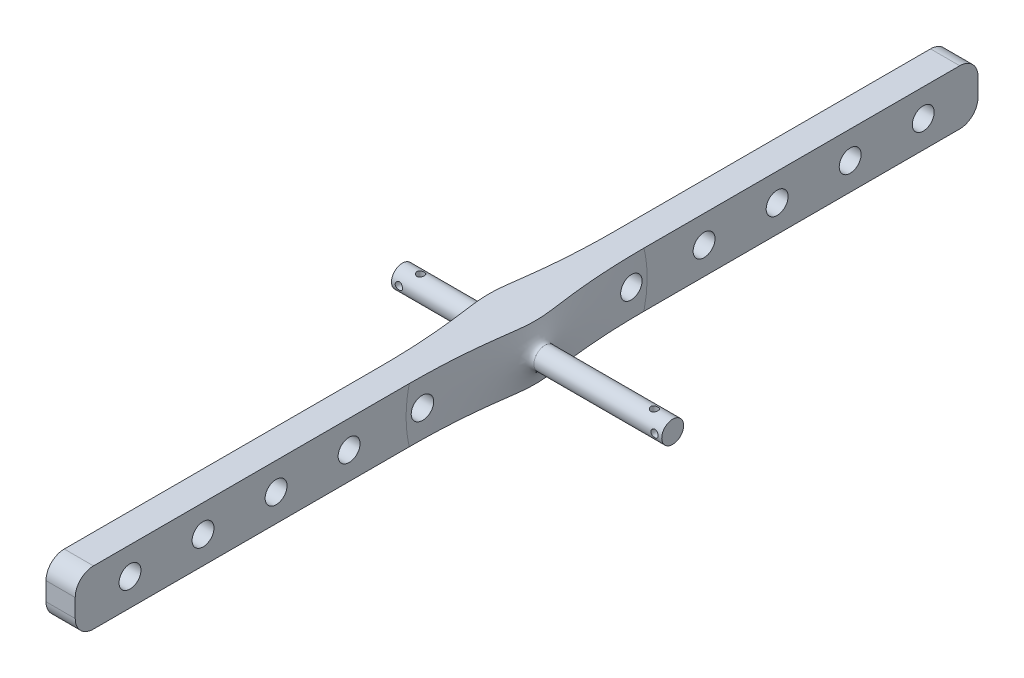
SolidWorks part; units mm, degrees
ref_plane "前视基准面" through (0, 0, 0) normal (0, 0, 1) x (1, 0, 0)
ref_plane "上视基准面" through (0, 0, 0) normal (0, 1, 0) x (1, 0, 0)
ref_plane "右视基准面" through (0, 0, 0) normal (1, 0, 0) x (0, 0, -1)
other "Configuration Table"
sketch "草图1" plane through (0, 0, 0) normal (1, 0, 0) x (0, 0, -1)
  line L1 (0, 0) -> (130, 0)
  line L2 (0, 0) -> (0, 15)
  line L3 (0, 15) -> (130, 15)
  line L4 (130, 0) -> (130, 15)
  dimension "D1" = 15
  dimension "D2" = 130
extrude "凸台-拉伸1" add sketch "草图1" along normal blind 8
sketch "草图15" plane through (0, 0, 0) normal (-1, 0, 0) x (0, 0, 1)
  line L0 (0, 15) -> (0, 0) construction
  circle A2 centre (-6.4, 7.5) radius 3
  dimension "D1" = 6
  dimension "D2" = 6.4
extrude "凸台-拉伸5" add sketch "草图15" along normal blind 26 and the other way blind 48
sketch "草图16" plane through (0, 0, 0) normal (0, 0, 1) x (1, 0, 0)
  line L0 (-26, 7.5) -> (-24.7951, 7.5) construction
  line L1 (-26, 10.5) -> (-26, 4.5) construction
  line L2 (48, 7.5) -> (28.4852, 7.5) construction
  line L3 (48, 4.5) -> (48, 10.5) construction
  circle A0 centre (-24, 7.5) radius 1
  circle A1 centre (46, 7.5) radius 1
  dimension "D2" = 2
  dimension "D3" = 2
  dimension "D1" = 2
  dimension "D4" = 2
extrude "切除-拉伸9" cut sketch "草图16" against normal up to next
sketch "草图17" plane through (0, 0, 0) normal (-1, 0, 0) x (0, 0, 1)
  line L0 (-130, 7.5) -> (-31.7081, 7.5) construction
  line L1 (-130, 0) -> (-130, 15) construction
  circle A0 centre (-115, 7.5) radius 3
  circle A1 centre (-95, 7.5) radius 3
  circle A2 centre (-75, 7.5) radius 3
  circle A3 centre (-55, 7.5) radius 3
  circle A4 centre (-35, 7.5) radius 3
  dimension "D6" = 6
  dimension "D7" = 6
  dimension "D8" = 6
  dimension "D9" = 6
  dimension "D10" = 6
  dimension "D1" = 15
  dimension "D2" = 20
  dimension "D3" = 20
  dimension "D4" = 20
  dimension "D5" = 20
extrude "切除-拉伸10" cut sketch "草图17" against normal up to next
sketch "草图18" plane through (0, 0, 0) normal (0, 1, 0) x (1, 0, 0)
  line L0 (-26, 6.4) -> (-12.4483, 6.4) construction
  line L1 (-26, 9.4) -> (-26, 3.4) construction
  line L2 (48, 3.4) -> (48, 9.4) construction
  circle A0 centre (-21, 6.4) radius 1
  circle A1 centre (43, 6.4) radius 1
  dimension "D2" = 2
  dimension "D4" = 2
  dimension "D1" = 5
  dimension "D3" = 5
extrude "切除-拉伸11" cut sketch "草图18" along normal blind 15
sketch "草图19" plane through (0, 0, 0) normal (0, 0, 1) x (1, 0, 0)
  line L1 (0, 15) -> (8, 15)
  line L2 (0, 15) -> (0, 0)
  line L3 (0, 0) -> (8, 0)
  line L4 (8, 15) -> (8, 0)
extrude "凸台-拉伸6" add sketch "草图19" along normal blind 117.2
ref_plane "基准面1" through (0, 0, -6.4) normal (0, 0, 1) x (1, 0, 0)
mirror "镜向1" about plane through (0, 0, -6.4) normal (0, 0, 1) of "切除-拉伸10"
fillet "圆角1" radius 5 4 edges at (4, 0, 117.2) (4, 15, 117.2) (4, 15, -130) (4, 0, -130)
fillet "圆角2" radius 30 1 edges at (0, 7.5, -3.4) second distance 5 first distance on face at (0, 7.5, 99.2)
fillet "圆角3" radius 5 1 edges at (8, 7.5, -3.4) second distance 30 first distance on face at (43.1709, 4.6664, -5.4147)
